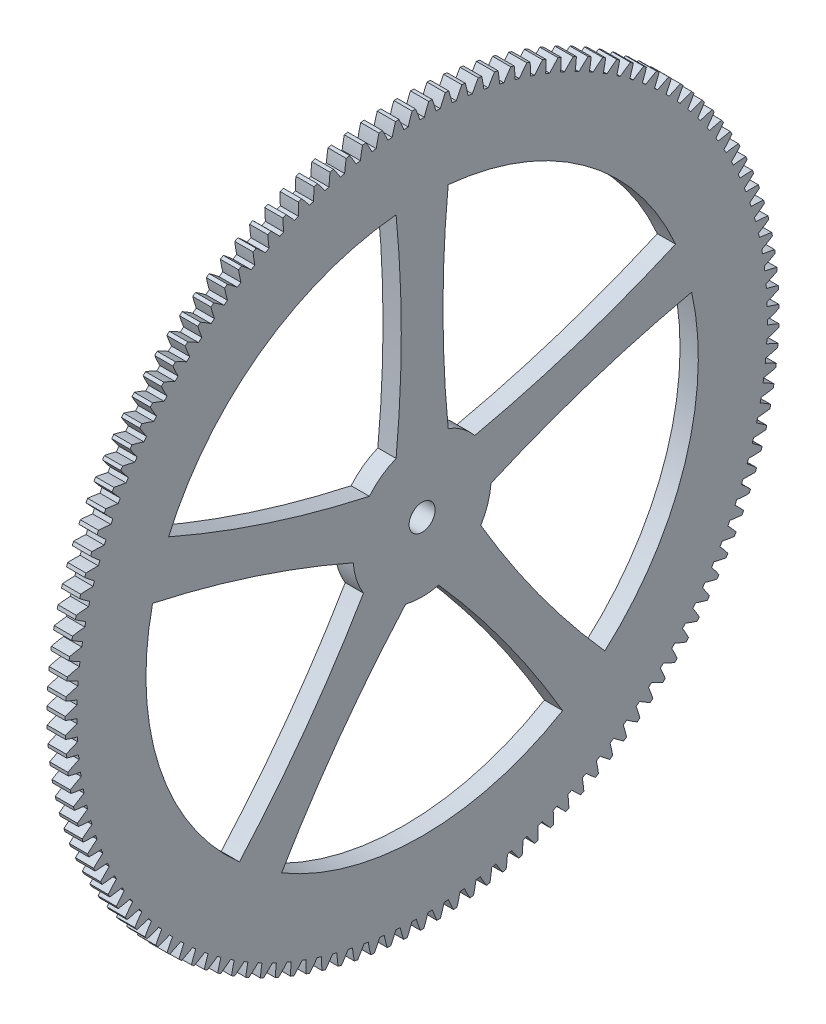
SolidWorks part; units mm, degrees
material "Cedar"
ref_plane "Plane1" through (0, 0, 0) normal (0, 0, 1) x (1, 0, 0)
ref_plane "Plane2" through (0, 0, 0) normal (0, 1, 0) x (1, 0, 0)
ref_plane "Plane3" through (0, 0, 0) normal (1, 0, 0) x (0, 0, -1)
sketch "HoldingSke" plane through (0, 0, 0) normal (0, 1, 0) x (1, 0, 0)
  line L0 (0, 0) -> (-359.2102, -359.2102)
  line L1 (-15, 0) -> (100, 0) construction
  line L2 (0, 0) -> (-2.1039, 2.3779)
  line L3 (0, 0) -> (-11.863, 4.5341)
  line L4 (0, 0) -> (-6.1066, 6.1066)
  line L5 (0, 0) -> (-47.5972, -17.7524)
  line L6 (0, 0) -> (-3.6847, -2.4861)
  line L7 (-2.1039, 2.3779) -> (8.8308, 51.9871)
  line L8 (-76.2, 54.61) -> (-69.596, 54.61)
  line L9 (-71.009, 38.7566) -> (-53.1078, 45.2721)
  line L10 (-76.2, 71.12) -> (104.1128, 71.12)
  line L11 (0, 0) -> (-4.445, 0)
  line L12 (-76.2, 101.6) -> (-76.1492, 101.6)
  line L13 (24.9733, 27.94) -> (52.9518, 28.4284)
  line L14 (24.9733, 27.94) -> (25.0241, 27.9398)
  line L15 (24.9733, 27.94) -> (100.4021, 29.52)
  circle A0 centre (0, 0) radius 3.175
  circle A1 centre (0, 0) radius 38.1
  circle A2 centre (0, 0) radius 38.1
  circle A3 centre (0, 0) radius 3.175
  dimension "MHD" = 76.2
  dimension "Hub_dia" = 76.2
  dimension "Bore" = 6.35
  dimension "MBD" = 6.35
  dimension "Num_teeth" = 135
  dimension "Pitch_radius" = 180.3128
  dimension "Pitch" = 508
  dimension "Width" = 4.445
  dimension "Overall_len" = 50.8
  dimension "Show_teeth" = 135
  dimension "Thickness" = 4.445
  dimension "OAL" = 50.8001
  dimension "T_dim" = 6.604
  dimension "Ap" = 20
  dimension "H" = 19.05
  dimension "Backlash" = 0.0508
  dimension "Addendum_fac" = 1
  dimension "Dedendum_fac" = 1.2
  dimension "Clearance_fac" = 0.2
  dimension "Dedendum_add" = 0.0508
sketch "BasProSke" plane through (0, 0, 0) normal (0, 1, 0) x (1, 0, 0)
  line L0 (-10, 0) -> (60, 0) construction
  line L1 (0, 0) -> (0, 86.995)
  line L2 (0, 0) -> (4.445, 0)
  line L3 (4.445, 0) -> (4.445, 86.995)
  line L4 (4.445, 86.995) -> (0, 86.995)
  dimension "Diameter" = 173.99
  dimension "Thickness" = 4.445
revolve "Base-Revolve" add sketch "BasProSke" angle 360 about L0
sketch "TooCutSke" plane through (0, 0, 0) normal (1, 0, 0) x (0, 0, -1)
  line L1 (0, 0) -> (0, 107) construction
  line L2 (0, 0) -> (-1.0863, 85.7181) construction
  line L3 (0, 0) -> (-3.9892, 171.394) construction
  line L4 (-1.0863, 85.7181) -> (-1.9946, 85.697) construction
  arc A0 (0.5277, 84.1485) -> (-0.5277, 84.1485) centre (0, 0) ccw
  arc A1 (1.6102, 87.0055) -> (-1.6102, 87.0055) centre (0, 0) ccw
  circle A2 centre (0, 0) radius 85.725 construction
  circle A3 centre (0, 0) radius 80.5551 construction
  arc A4 (-0.5277, 84.1485) -> (-1.6102, 87.0055) centre (-33.1026, 73.4395) ccw
  arc A5 (1.6102, 87.0055) -> (0.5277, 84.1485) centre (33.1026, 73.4395) ccw
  dimension "Root_dia" = 168.3004
  dimension "Overcut_dia" = 174.0408
  dimension "Pitch_dia" = 171.45
  dimension "Base_dia" = 161.1103
  dimension "Flank_rad" = 34.29
  dimension "Half_ang" = 1.333
  dimension "Half_CT" = 0.9085
extrude "ToothCut" cut sketch "TooCutSke" along normal through all
fillet "Breaks" [suppressed] radius 0.0254 tangent propagation no
fillet "RootFillets" [suppressed] radius 0.3048
pattern_circular "TeethCuts" count 135 every 2.667 about axis through (-10, 0, 0) along (1, 0, 0) of "ToothCut", "RootFillets", "Breaks"
sketch "HubNeaOneSke" plane through (0, 0, 0) normal (-1, 0, 0) x (0, 0, 1)
  circle A0 centre (0, 0) radius 38.1
  dimension "Diameter" = 76.2
extrude "HubNearOne" [suppressed] add sketch "HubNeaOneSke" along normal blind 46.3551
sketch "HubNeaBotSke" plane through (0, 0, 0) normal (-1, 0, 0) x (0, 0, 1)
  circle A0 centre (0, 0) radius 38.1
  dimension "Diameter" = 76.2
extrude "HubNearBoth" [suppressed] add sketch "HubNeaBotSke" along normal blind 23.1775
ref_plane "FarPln" through (4.445, 0, 0) normal (1, 0, 0) x (0, 0, -1)
sketch "HubFarSke" plane through (4.445, 0, 0) normal (1, 0, 0) x (0, 0, -1)
  circle A0 centre (0, 0) radius 38.1
  dimension "Diameter" = 76.2
extrude "HubFar" [suppressed] add sketch "HubFarSke" along normal blind 23.1775
sketch "BorSke" plane through (0, 0, 0) normal (1, 0, 0) x (0, 0, -1)
  circle A0 centre (0, 0) radius 3.175
  dimension "Diameter" = 6.35
extrude "Bore" cut sketch "BorSke" along normal mid plane 101.6001
sketch "KeySke" plane through (0, 0, 0) normal (1, 0, 0) x (0, 0, -1)
  line L0 (-0.127, 0) -> (-0.127, 3.429)
  line L1 (-0.127, 3.429) -> (0.127, 3.429)
  line L2 (0.127, 3.429) -> (0.127, 0)
  line L3 (0, 0) -> (0, 34) construction
  line L4 (-0.127, 0) -> (0.127, 0)
  dimension "Offset" = 3.429
  dimension "Width" = 0.254
extrude "Keyway" [suppressed] cut sketch "KeySke" along normal mid plane 101.6001
pattern_circular "Keyway2" [suppressed] count 2 every 90 about axis through (-10, 0, 0) along (1, 0, 0)
sketch "Sketch1" plane through (0, 0, 0) normal (-1, 0, 0) x (0, 0, 1)
  line L0 (6.35, 67.02) -> (-6.35, 67.02)
  line L1 (6.35, 67.02) -> (6.35, 15.5861)
  line L2 (-6.35, 67.02) -> (-6.35, 15.5861)
  line L3 (6.35, 15.5861) -> (-6.35, 15.5861)
  line L4 (65.7021, 14.6711) -> (16.7856, -1.2228)
  line L5 (34.2561, -57.9528) -> (4.024, -16.3419)
  line L6 (-44.5306, -50.4879) -> (-14.2986, -8.877)
  line L7 (-61.7776, 26.7495) -> (-12.861, 10.8556)
  circle A0 centre (0, 0) radius 16.83
  circle A1 centre (0, 0) radius 67.3202
  arc A2 (6.35, 67.02) -> (6.35, 15.5861) centre (266.0932, 41.3031) ccw
  arc A3 (-6.35, 67.02) -> (-6.35, 15.5861) centre (-266.0932, 41.3031) cw
  arc A4 (65.7021, 14.6711) -> (16.7856, -1.2228) centre (121.5089, -240.3063) ccw
  arc A5 (61.7776, 26.7495) -> (12.861, 10.8556) centre (-42.9458, 265.8331) cw
  arc A6 (34.2561, -57.9528) -> (4.024, -16.3419) centre (-190.9966, -189.8206) ccw
  arc A7 (44.5306, -50.4879) -> (14.2986, -8.877) centre (239.5513, 122.9908) cw
  arc A8 (-44.5306, -50.4879) -> (-14.2986, -8.877) centre (-239.5513, 122.9908) ccw
  arc A9 (-34.2561, -57.9528) -> (-4.024, -16.3419) centre (190.9966, -189.8206) cw
  arc A10 (-61.7776, 26.7495) -> (-12.861, 10.8556) centre (42.9458, 265.8331) ccw
  arc A11 (-65.7021, 14.6711) -> (-16.7856, -1.2228) centre (-121.5089, -240.3063) cw
  point P4 (0, 67.3202)
  point P5 (0, 67.02)
  point P10 (-5.08, 41.3031)
  point P11 (5.08, 41.3031)
  point P41 (0, 0)
  dimension "D1" = 33.6601
  dimension "D2" = 134.6403
  dimension "D5" = 5
  dimension "D4" = 10.16
  dimension "D3" = 12.7
extrude "Cut-Extrude1" cut sketch "Sketch1" against normal through all contours A1 A0 | L1 A2 | A3 L2 | L2 A1 L7 A0 | A11 A1 L6 A0 | A9 A1 L5 A0 | A7 A1 L4 A0 | L4 A4 | L5 A6 | L6 A8 | L7 A10 region at (0, 37.4142, 27.6921) region at (0, 41.3031, 5.8419) region at (0, 41.3031, -5.8419) region at (0, 37.8251, -27.4815) region at (0, 18.3193, -37.4763) region at (0, -14.7752, 44.1403) region at (0, 7.2074, 41.0868) region at (0, -13.9917, -44.3949) region at (0, -29.9811, -29.0035) region at (0, -46.5457, -0.4119) region at (0, -36.8487, 19.5511)
equation "' \"Pitch@HoldingSke\" = 4"
equation "' \"Num_teeth@HoldingSke\" = 12"
equation "' \"Ap@HoldingSke\" =  20"
equation "' \"Width@HoldingSke\" = 0.5"
equation "' \"Hub_dia@HoldingSke\"= 1"
equation "' \"Overall_len@HoldingSke\" = 1.0"
equation "' \"Bore@HoldingSke\" = 0.75"
equation "' \"T_dim@HoldingSke\" = 0.85"
equation "' \"Width@KeySke\" = 0.25"
equation "' \"Show_teeth@HoldingSke\" = 13"
equation "' \"Backlash@HoldingSke\" = 0.009"
equation "' \"Addendum_fac@HoldingSke\" = 1.0"
equation "' \"Dedendum_fac@HoldingSke\" = 1.25"
equation "' \"Dedendum_add@HoldingSke\" = 0.00005"
equation "' \"Clearance_fac@HoldingSke\" = 0.25"
equation "' \"Pitch@HoldingSke\" = 0.5"
equation "' \"Num_teeth@HoldingSke\" = 23"
equation "' \"Show_teeth@HoldingSke\" = 23"
equation "' \"Backlash@HoldingSke\" = 0.0375"
equation "\"Overcut_dia@TooCutSke\" = (\"Num_teeth@HoldingSke\" + 2 * \"Addendum_fac@HoldingSke\") / \"Pitch@HoldingSke\" + 0.002"
equation "\"Pitch_dia@TooCutSke\" = \"Num_teeth@HoldingSke\" / \"Pitch@HoldingSke\""
equation "\"Base_dia@TooCutSke\" = \"Num_teeth@HoldingSke\" / \"Pitch@HoldingSke\" * cos((\"Ap@HoldingSke\"  * 3.14159265 / 180))"
equation "\"Root_dia@TooCutSke\" = (\"Num_teeth@HoldingSke\" + 2) / \"Pitch@HoldingSke\" - 2 * (\"Addendum_fac@HoldingSke\" + \"Dedendum_fac@HoldingSke\") / \"Pitch@HoldingSke\" - \"Dedendum_add@HoldingSke\" * 2"
equation "\"Half_ang@TooCutSke\" = 180 / \"Num_teeth@HoldingSke\""
equation "\"Half_CT@TooCutSke\" = \"Num_teeth@HoldingSke\" / \"Pitch@HoldingSke\" * sin((3.14159265 / 2 / \"Num_teeth@HoldingSke\")) / 2 - 7 * \"Backlash@HoldingSke\" / 4"
equation "\"Flank_rad@TooCutSke\" = \"Num_teeth@HoldingSke\" / \"Pitch@HoldingSke\" / 5"
equation "\"Radius@RootFillets\" = \"Clearance_fac@HoldingSke\" / \"Pitch@HoldingSke\" + \"Dedendum_add@HoldingSke\""
equation "\"Break_rad@Breaks\" = 0.02 / \"Pitch@HoldingSke\""
equation "\"Thickness@HoldingSke\" = \"Width@HoldingSke\""
equation "\"OAL@HoldingSke\" = \"Thickness@HoldingSke\""
equation "\"MHD@HoldingSke\" = (\"Num_teeth@HoldingSke\" + 2) / \"Pitch@HoldingSke\" - 2 * (\"Addendum_fac@HoldingSke\" + \"Dedendum_fac@HoldingSke\")  / \"Pitch@HoldingSke\" - \"Dedendum_add@HoldingSke\" * 2"
equation "\"MBD@HoldingSke\" = (\"Num_teeth@HoldingSke\" + 2) / \"Pitch@HoldingSke\" - 2 * (\"Addendum_fac@HoldingSke\" + \"Dedendum_fac@HoldingSke\")  / \"Pitch@HoldingSke\" - \"Dedendum_add@HoldingSke\" * 2 - 0.002"
equation "\"MHD@HoldingSke\" = ((sgn( \"MHD@HoldingSke\" - \"Hub_dia@HoldingSke\" )-1)*( \"MHD@HoldingSke\" - \"Hub_dia@HoldingSke\" ))/-2+ \"Hub_dia@HoldingSke\""
equation "\"MBD@HoldingSke\" = ((sgn( \"MBD@HoldingSke\" - \"Bore@HoldingSke\" )-1)*( \"MBD@HoldingSke\" - \"Bore@HoldingSke\" ))/-2+ \"Bore@HoldingSke\""
equation "\"OAL@HoldingSke\" = ((sgn( \"OAL@HoldingSke\" - \"Overall_len@HoldingSke\" )+1)*( \"OAL@HoldingSke\" - \"Overall_len@HoldingSke\" ))/2 + \"Overall_len@HoldingSke\" + 0.000002"
equation "\"Num_teeth@TeethCuts\" = int( \"Show_teeth@HoldingSke\" ) + 1"
equation "\"Num_teeth@TeethCuts\" = ((sgn( \"Num_teeth@TeethCuts\" - \"Num_teeth@HoldingSke\" )-1)*( \"Num_teeth@TeethCuts\" - \"Num_teeth@HoldingSke\" ))/-2+ \"Num_teeth@HoldingSke\""
equation "\"Num_teeth@TeethCuts\" = ((sgn( \"Num_teeth@TeethCuts\" - 2.0)+1)*( \"Num_teeth@TeethCuts\" - 2.0))/2 +2.0"
equation "\"Angle@TeethCuts\" = 360.0 / \"Num_teeth@HoldingSke\""
equation "\"Diameter@BasProSke\" = (\"Num_teeth@HoldingSke\" + 2 * \"Addendum_fac@HoldingSke\") / \"Pitch@HoldingSke\""
equation "\"Thickness@BasProSke\"  = \"Thickness@HoldingSke\""
equation "' \"Fillet_rad@BasProSke\" =  \"Thickness@HoldingSke\" * 0.05"
equation "\"MHD@HoldingSke\" = ((sgn( \"MHD@HoldingSke\" - \"Root_dia@TooCutSke\" )-1)*( \"MHD@HoldingSke\" - \"Root_dia@TooCutSke\" ))/-2+ \"Root_dia@TooCutSke\""
equation "\"Diameter@HubNeaOneSke\" = \"MHD@HoldingSke\""
equation "\"Length@HubNearOne\" = \"OAL@HoldingSke\" - \"Thickness@BasProSke\""
equation "\"Diameter@HubNeaBotSke\" = \"MHD@HoldingSke\""
equation "\"Length@HubNearBoth\" = ( \"OAL@HoldingSke\" - \"Thickness@BasProSke\" ) / 2.0"
equation "\"Thickness@FarPln\" = \"Thickness@BasProSke\""
equation "\"Diameter@HubFarSke\" = \"MHD@HoldingSke\""
equation "\"Length@HubFar\" = ( \"OAL@HoldingSke\" - \"Thickness@BasProSke\" ) / 2.0"
equation "\"Diameter@BorSke\" = \"MBD@HoldingSke\""
equation "\"D1@Bore\" = \"OAL@HoldingSke\" * 2.0"
equation "\"D1@Keyway\" = \"OAL@HoldingSke\" * 2.0"
equation "\"Offset@KeySke\" = \"T_dim@HoldingSke\" - \"MBD@HoldingSke\" / 2.0"
